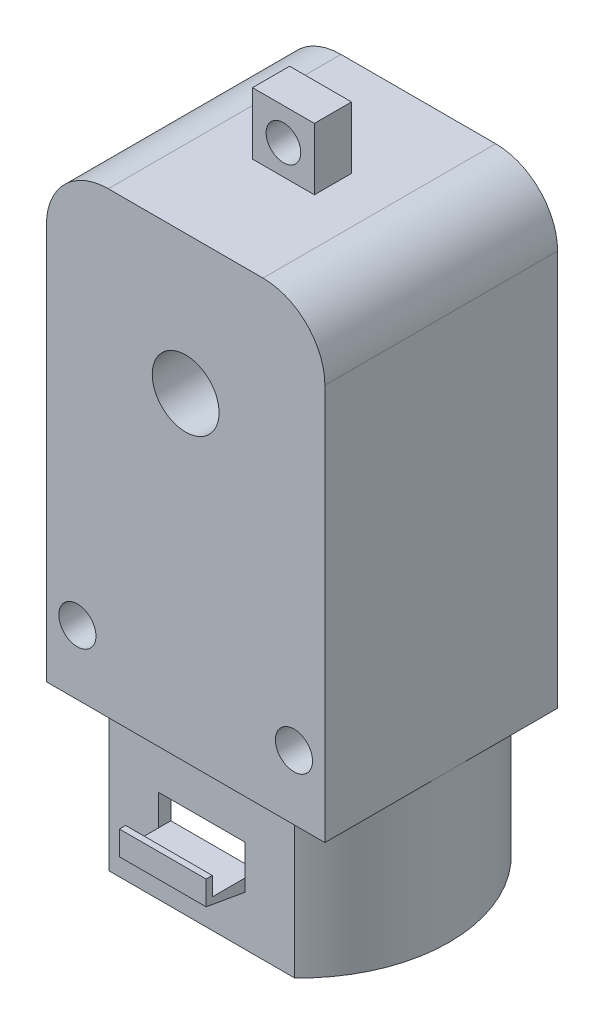
SolidWorks part; units mm, degrees
material "PBT General Purpose"
ref_plane "Alzado" through (0, 0, 0) normal (0, 0, 1) x (1, 0, 0)
ref_plane "Planta" through (0, 0, 0) normal (0, 1, 0) x (1, 0, 0)
ref_plane "Vista lateral" through (0, 0, 0) normal (1, 0, 0) x (0, 0, -1)
sketch "Croquis2" plane through (0, 0, 0) normal (0, 0, 1) x (1, 0, 0)
  line L0 (2.5, -31.8) -> (20, -31.8) construction
  line L1 (5, 0) -> (17.5, 0)
  line L2 (0, -5) -> (0, -37)
  line L3 (0, -37) -> (22.5, -37)
  line L4 (22.5, -5) -> (22.5, -37)
  circle A0 centre (2.5, -31.8) radius 1.5
  circle A1 centre (20, -31.8) radius 1.5
  arc A2 (22.5, -5) -> (17.5, 0) centre (17.5, -5) ccw
  arc A3 (0, -5) -> (5, 0) centre (5, -5) cw
  point P9 (11.25, -37)
  point P10 (11.25, -31.8)
  point P13 (22.5, 0)
  point P16 (0, 0)
  dimension "D3" = 3
  dimension "D4" = 3
  dimension "D7" = 5
  dimension "D1" = 22.5
  dimension "D2" = 37
  dimension "D5" = 17.5
  dimension "D6" = 31.8
extrude "Saliente-Extruir1" add sketch "Croquis2" along normal mid plane 18.8
sketch "Croquis3" plane through (0, 0, 0) normal (0, 0, 1) x (1, 0, 0)
  line L0 (17.5, 0) -> (5, 0) construction
  line L1 (8.75, 0) -> (13.75, 0)
  line L2 (8.75, 0) -> (8.75, 5)
  line L3 (8.75, 5) -> (13.75, 5)
  line L4 (13.75, 0) -> (13.75, 5)
  circle A0 centre (11.25, 2.4) radius 1.4
  point P6 (11.25, 0)
  point P7 (11.25, 5)
  dimension "D3" = 2.8
  dimension "D1" = 5
  dimension "D2" = 5
  dimension "D4" = 2.4
extrude "Saliente-Extruir2" add sketch "Croquis3" along normal mid plane 3
sketch "Croquis5" plane through (0, -37, 0) normal (0, -1, 0) x (1, 0, 0)
  line L0 (18.75, -9.4) -> (3.75, -9.4)
  line L1 (0, -9.4) -> (22.5, -9.4) construction
  line L2 (11.25, -9.4) -> (11.25, 8.1) construction
  line L3 (0, 8.1) -> (11.25, 8.1) construction
  line L4 (0, 9.4) -> (0, -9.4) construction
  line L5 (0, 9.4) -> (22.5, 9.4) construction
  line L6 (3.75, 8.1) -> (18.75, 8.1)
  line L7 (0, 9.4) -> (0, -9.4) construction
  line L8 (4.1601, 7.1) -> (18.3399, 7.1)
  line L9 (18.3399, -8.4) -> (4.1601, -8.4)
  arc A0 (3.75, -9.4) -> (3.75, 8.1) centre (12.0833, -0.65) cw
  arc A1 (18.75, -9.4) -> (18.75, 8.1) centre (10.4167, -0.65) ccw
  arc A2 (4.1601, -8.4) -> (4.1601, 7.1) centre (12.0833, -0.65) cw
  arc A3 (18.3399, -8.4) -> (18.3399, 7.1) centre (10.4167, -0.65) ccw
  point P7 (11.25, 9.4)
  point P18 (11.25, 8.1)
  dimension "D3" = 15
  dimension "D1" = 15
  dimension "D2" = 17.5
  dimension "D4" = 1
extrude "Saliente-Extruir3" add sketch "Croquis5" along normal blind 12
sketch "Croquis6" plane through (0, 0, 8.1) normal (0, 0, 1) x (1, 0, 0)
  line L0 (0, -37) -> (22.5, -37) construction
  line L1 (7.75, -41.5) -> (14.75, -41.5)
  line L2 (7.75, -41.5) -> (7.75, -44)
  line L3 (7.75, -44) -> (14.75, -44)
  line L4 (14.75, -41.5) -> (14.75, -44)
  line L5 (18.75, -49) -> (18.75, -37) construction
  dimension "D1" = 7
  dimension "D2" = 11
  dimension "D3" = 7
  dimension "D4" = 2.5
extrude "Cortar-Extruir1" cut sketch "Croquis6" against normal through all
sketch "Croquis7" plane through (0, 0, 0) normal (1, 0, 0) x (0, 0, -1)
  line L0 (0, 5) -> (0, -49) construction
  line L1 (-1.5, 5) -> (1.5, 5) construction
  line L2 (-8.1, -49) -> (9.4, -49) construction
  line L3 (-8.1, -49) -> (-8.1, -44) construction
  line L4 (-8.1, -49) -> (-8.1, -37) construction
  line L5 (-8.1, -44) -> (-10.75, -44)
  line L6 (-10.75, -44) -> (-10.75, -42.5)
  line L7 (-10.75, -42.5) -> (-11.25, -42.5)
  line L8 (-11.25, -42.5) -> (-11.25, -44.4446)
  line L9 (-11.25, -44.4446) -> (-8.1, -45)
  line L10 (-8.1, -45) -> (-8.1, -44)
  dimension "D1" = 5
  dimension "D2" = 22.5
  dimension "D3" = 0.5
  dimension "D4" = 1.5
  dimension "D5" = 1
  dimension "D6" = 100
extrude "Saliente-Extruir4" add sketch "Croquis7" along normal up to surface (14.75 mm away) from surface up to face at (14.75, -42.75, 7.6) starting at face at (7.75, -42.75, 7.6)
ref_plane "Plano1" through (0, 0, -0.65) normal (0, 0, -1) x (-1, 0, 0)
mirror "Simetría1" about plane through (0, 0, -0.65) normal (0, 0, -1) of "Saliente-Extruir4"
sketch "Croquis8" plane through (0, 0, -9.4) normal (0, 0, -1) x (-1, 0, 0)
  line L0 (-11.25, 0) -> (-11.25, -11.2) construction
  line L1 (-17.5, 0) -> (-5, 0) construction
  line L2 (-11.25, -11.2) -> (0, -11.2) construction
  line L3 (0, -5) -> (0, -37) construction
  circle A0 centre (-11.25, -11.2) radius 2.7
  dimension "D1" = 2.7
  dimension "D2" = 11.2
extrude "Cortar-Extruir2" cut sketch "Croquis8" against normal through all
